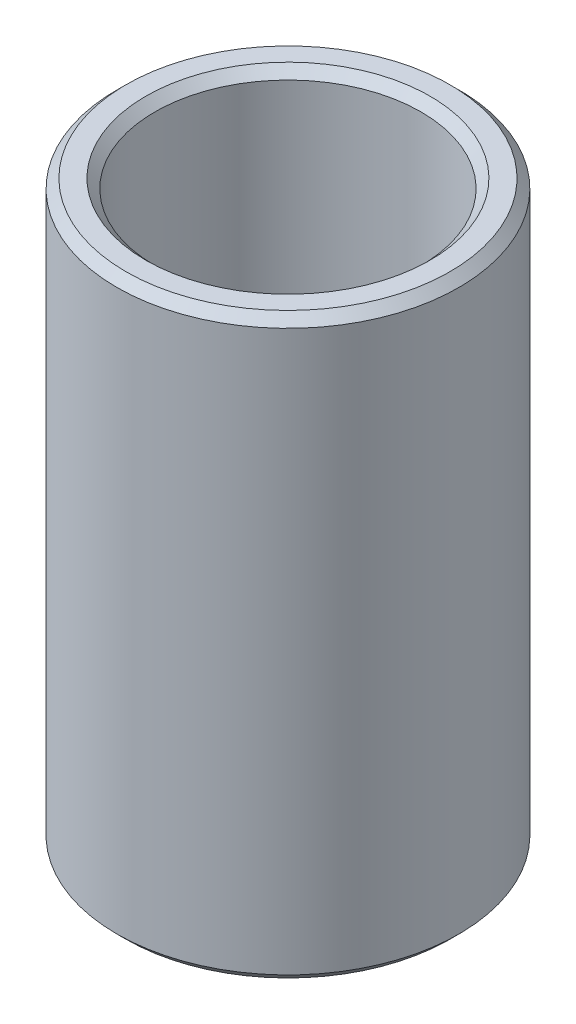
SolidWorks part; units mm, degrees
ref_plane "Front Plane" through (0, 0, 0) normal (0, 0, 1) x (1, 0, 0)
ref_plane "Top Plane" through (0, 0, 0) normal (0, 1, 0) x (1, 0, 0)
ref_plane "Right Plane" through (0, 0, 0) normal (1, 0, 0) x (0, 0, -1)
sketch "Sketch1" plane through (0, 0, 0) normal (0, 1, 0) x (1, 0, 0)
  circle A0 centre (0, 0) radius 55
  dimension "SLEEVE_OD" = 110
extrude "Boss-Extrude1" add sketch "Sketch1" along normal blind 185.8666
sketch "Sketch2" plane through (0, 0, 0) normal (0, 1, 0) x (1, 0, 0)
  circle A0 centre (0, 0) radius 42.7799
  dimension "BORE_D" = 85.5599
extrude "Cut-Extrude1" cut sketch "Sketch2" along normal through all
chamfer "Chamfer1" distance 2.9176 angle 45 4 edges at (0, 185.8666, 42.7799) (0, 0, 42.7799) (0, 0, 55) (0, 185.8666, 55)
